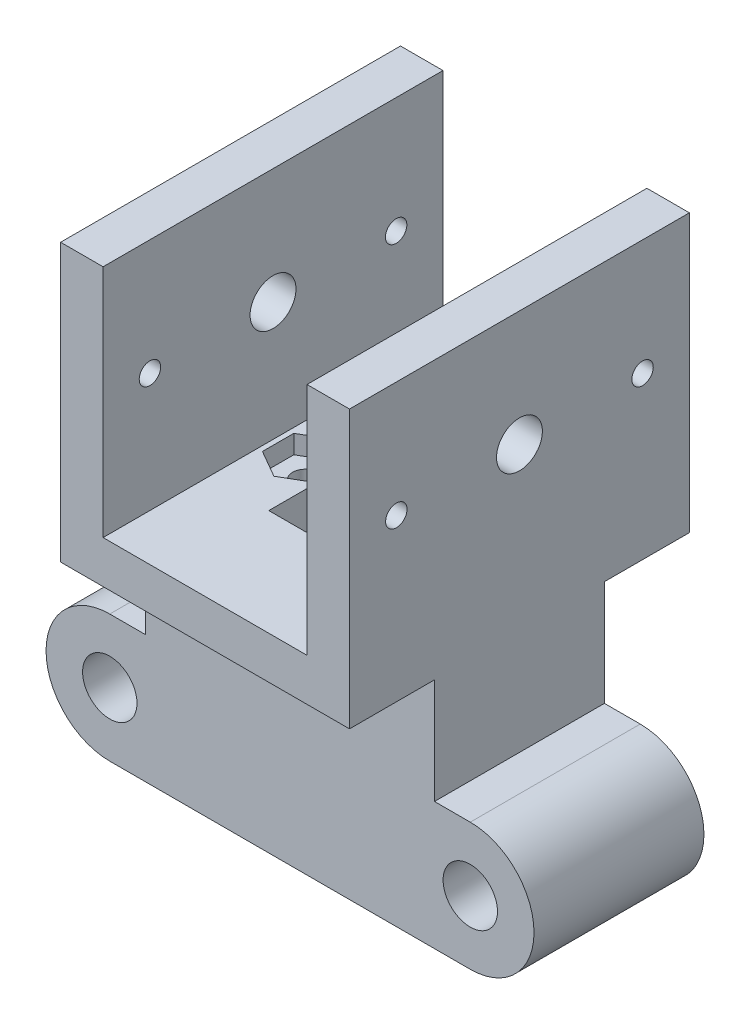
SolidWorks part; units mm, degrees
ref_plane "Front Plane" through (0, 0, 0) normal (0, 0, 1) x (1, 0, 0)
ref_plane "Top Plane" through (0, 0, 0) normal (0, 1, 0) x (1, 0, 0)
ref_plane "Right Plane" through (0, 0, 0) normal (1, 0, 0) x (0, 0, -1)
sketch "Sketch1" plane through (0, 0, 0) normal (0, 0, 1) x (1, 0, 0)
  line L0 (-26.9408, -26.9408) -> (0, 0) construction
  line L1 (0, 0) -> (26.9408, -26.9408) construction
  line L2 (-45.4545, 0) -> (50.5549, 0) construction
  line L7 (-26.9408, -17.4158) -> (-26.9408, 39.7342)
  line L9 (26.9408, 39.7342) -> (26.9408, -17.4158)
  line L11 (15, -48.5349) -> (-15, -48.5349) construction
  line L12 (-26.9408, -36.4658) -> (26.9408, -36.4658)
  line L13 (-26.9408, 39.7342) -> (26.9408, 39.7342)
  circle A0 centre (0, 0) radius 38.1 construction
  circle A1 centre (-26.9408, -26.9408) radius 4.064
  circle A2 centre (26.9408, -26.9408) radius 4.064
  arc A3 (-26.9408, -17.4158) -> (-26.9408, -36.4658) centre (-26.9408, -26.9408) ccw
  arc A4 (26.9408, -36.4658) -> (26.9408, -17.4158) centre (26.9408, -26.9408) ccw
  circle A5 centre (0, 0) radius 50.8 construction
  dimension "D1" = 76.2
  dimension "D4" = 8.128
  dimension "D5" = 8.128
  dimension "D6" = 19.05
  dimension "D7" = 19.05
  dimension "D8" = 57.15
  dimension "D9" = 101.6
  dimension "D2" = 45
  dimension "D3" = 45
  dimension "D10" = 30
extrude "Boss-Extrude1" add sketch "Sketch1" along normal blind 12.7 and the other way blind 12.7
sketch "Sketch9" plane through (0, 0, 12.7) normal (0, 0, 1) x (1, 0, 0)
  line L0 (-26.9408, 39.7342) -> (26.9408, 39.7342) construction
  line L1 (-15.24, 39.7342) -> (15.24, 39.7342)
  line L2 (-15.24, 39.7342) -> (-15.24, 4.6822)
  line L3 (-15.24, 4.6822) -> (15.24, 4.6822)
  line L4 (15.24, 39.7342) -> (15.24, 4.6822)
  line L5 (-15.24, 39.7342) -> (15.24, 4.6822) construction
  line L6 (-15.24, 4.6822) -> (15.24, 39.7342) construction
  point P0 (0, 22.2082)
  dimension "D1" = 30.48
  dimension "D2" = 35.052
extrude "Cut-Extrude6" cut sketch "Sketch9" against normal through all
sketch "Sketch10" plane through (0, 0, 12.7) normal (0, 0, 1) x (1, 0, 0)
  line L0 (-26.9408, 39.7342) -> (-26.9408, -1.6678)
  line L2 (-26.9408, -1.6678) -> (26.9408, -1.6678)
  line L3 (26.9408, 39.7342) -> (26.9408, -17.4158) construction
  line L5 (26.9408, -1.6678) -> (26.9408, 39.7342)
  line L6 (26.9408, 39.7342) -> (15.24, 39.7342)
  line L7 (15.24, 39.7342) -> (15.24, 4.6822)
  line L8 (15.24, 4.6822) -> (-15.24, 4.6822)
  line L9 (-15.24, 4.6822) -> (-15.24, 39.7342)
  line L10 (-15.24, 39.7342) -> (-26.9408, 39.7342)
  dimension "D1" = 6.35
extrude "Boss-Extrude3" add sketch "Sketch10" along normal blind 12.7
mirror "Mirror4" about plane through (0, 0, 0) normal (0, 0, 1) of "Boss-Extrude3"
sketch "Sketch11" plane through (0, 0, 25.4) normal (0, 0, 1) x (1, 0, 0)
  line L1 (-26.9408, 39.7342) -> (-21.59, 39.7342)
  line L2 (-26.9408, 39.7342) -> (-26.9408, -17.4158)
  line L3 (-26.9408, -17.4158) -> (-21.59, -17.4158)
  line L4 (-21.59, 39.7342) -> (-21.59, -17.4158)
  line L5 (-15.24, 4.6822) -> (-15.24, 39.7342) construction
  dimension "D1" = 6.35
extrude "Cut-Extrude7" cut sketch "Sketch11" against normal through all
mirror "Mirror5" about plane through (0, 0, 0) normal (1, 0, 0) of "Cut-Extrude7"
sketch "Sketch12" plane through (0, -36.4658, 0) normal (0, -1, 0) x (1, 0, 0)
  line L1 (-6.35, 9.525) -> (6.35, 9.525)
  line L2 (-6.35, 9.525) -> (-6.35, -9.525)
  line L3 (-6.35, -9.525) -> (6.35, -9.525)
  line L4 (6.35, 9.525) -> (6.35, -9.525)
  line L5 (-6.35, 9.525) -> (6.35, -9.525) construction
  line L6 (-6.35, -9.525) -> (6.35, 9.525) construction
  point P0 (0, 0)
  dimension "D1" = 19.05
  dimension "D2" = 12.7
extrude "Cut-Extrude8" cut sketch "Sketch12" against normal through all
sketch "Sketch14" plane through (-21.59, 0, 0) normal (-1, 0, 0) x (0, 0, 1)
  line L0 (-25.4, 4.6822) -> (25.4, 4.6822) construction
  circle A0 centre (-18.4, 22.4622) radius 1.6
  dimension "D1" = 3.2
  dimension "D2" = 17.78
  dimension "D3" = 18.4
extrude "Cut-Extrude9" cut sketch "Sketch14" against normal through all
mirror "Mirror6" about plane through (0, 0, 0) normal (0, 0, 1) of "Cut-Extrude9"
sketch "Sketch15" plane through (21.59, 0, 0) normal (1, 0, 0) x (0, 0, -1)
  line L0 (0, -17.4158) -> (0, 39.7342) construction
  line L1 (-18.4, 22.4622) -> (18.4, 22.4622) construction
  line L2 (0, 38.1) -> (0, -38.1) construction
  circle A0 centre (0, 22.4622) radius 3.429
  dimension "D1" = 6.858
extrude "Cut-Extrude10" cut sketch "Sketch15" against normal through all
sketch "Sketch18" plane through (0, 4.6822, 0) normal (0, 1, 0) x (1, 0, 0)
  line L0 (-26.9408, 0) -> (26.9408, 0) construction
  line L1 (-6.35, 2.3464) -> (-10.414, 4.6927)
  line L2 (-10.414, 4.6927) -> (-14.478, 2.3464)
  line L3 (-14.478, 2.3464) -> (-14.478, -2.3464)
  line L4 (-14.478, -2.3464) -> (-10.414, -4.6927)
  line L5 (-10.414, -4.6927) -> (-6.35, -2.3464)
  line L6 (-6.35, -2.3464) -> (-6.35, 2.3464)
  line L7 (-6.35, -9.525) -> (-6.35, 9.525) construction
  circle A0 centre (-10.414, 0) radius 4.064 construction
  dimension "D1" = 8.128
extrude "Cut-Extrude11" cut sketch "Sketch18" against normal blind 2.7781
mirror "Mirror7" about plane through (0, 0, 0) normal (1, 0, 0) of "Cut-Extrude11"
hole_wizard "#6 Clearance Hole1" positions "Sketch20" profile "Sketch22" hole size "#6" standard "ANSI Inch" end condition through all
sketch "Sketch20" plane through (0, 1.9041, 0) normal (0, 1, 0) x (1, 0, 0)
  line L0 (-26.9408, 0) -> (26.9408, 0) construction
  line L1 (-10.414, 4.6927) -> (-10.414, -4.6927) construction
  point P0 (-10.414, 0)
sketch "Sketch22" plane through (-10.414, 1.9041, 0) normal (1, 0, 0) x (0, 0, 1)
  line L0 (0, 0) -> (0, 38.3699)
  line L1 (0, 38.3699) -> (1.8986, 38.3699)
  line L2 (1.8986, 38.3699) -> (1.8986, 0)
  line L5 (1.8986, 0) -> (0, 0)
  line L11 (0, -6.35) -> (0, 107.95) construction
  dimension "Thru Hole Dia." = 3.7973
  dimension "Thru Hole Depth" = 38.3699
mirror "Mirror8" about plane through (0, 0, 0) normal (1, 0, 0) of "#6 Clearance Hole1"
sketch "Sketch23" plane through (0, -36.4658, 0) normal (0, -1, 0) x (1, 0, 0)
  circle A0 centre (-10.414, 0) radius 3.175
  circle A1 centre (10.414, 0) radius 3.175
  dimension "D1" = 6.35
  dimension "D2" = 6.35
extrude "Cut-Extrude12" cut sketch "Sketch23" against normal blind 22.225
sketch "Sketch24" plane through (0, 0, -12.7) normal (0, 0, -1) x (-1, 0, 0)
  line L0 (21.59, -1.6678) -> (-21.59, -1.6678) construction
  line L1 (-6.35, -11.1928) -> (6.35, -11.1928)
  line L2 (-6.35, -11.1928) -> (-6.35, -30.2428)
  line L3 (-6.35, -30.2428) -> (6.35, -30.2428)
  line L4 (6.35, -11.1928) -> (6.35, -30.2428)
  line L5 (-6.35, -11.1928) -> (6.35, -30.2428) construction
  line L6 (-6.35, -30.2428) -> (6.35, -11.1928) construction
  point P0 (0, -20.7178)
  dimension "D1" = 12.7
  dimension "D2" = 19.05
  dimension "D3" = 19.05
extrude "Cut-Extrude13" cut sketch "Sketch24" against normal up to next
